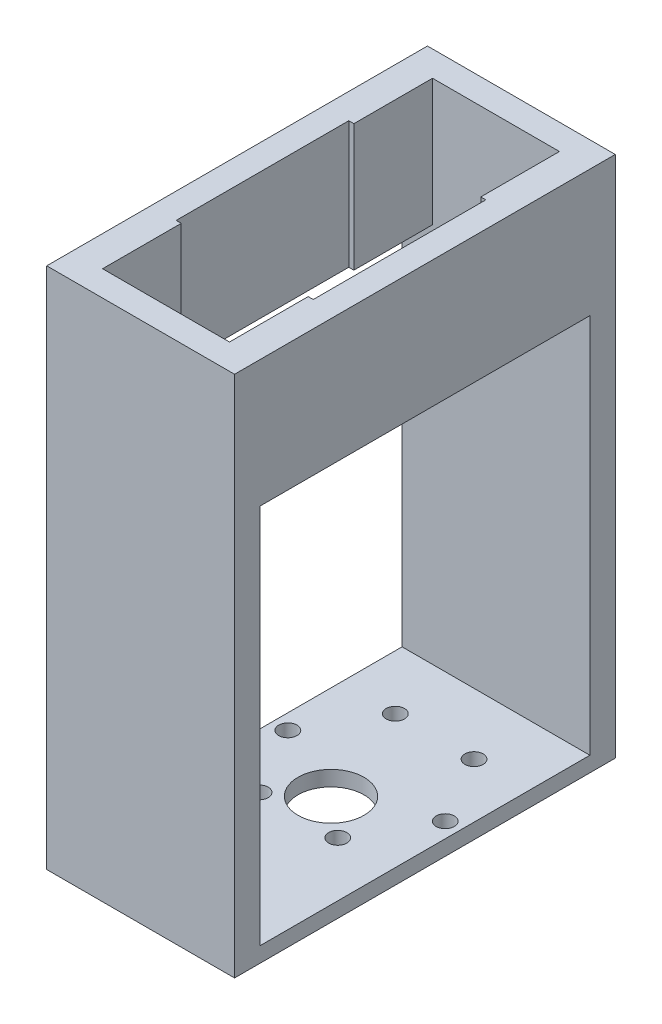
SolidWorks part; units mm, degrees
ref_plane "Front Plane" through (0, 0, 0) normal (0, 0, 1) x (1, 0, 0)
ref_plane "Top Plane" through (0, 0, 0) normal (0, 1, 0) x (1, 0, 0)
ref_plane "Right Plane" through (0, 0, 0) normal (1, 0, 0) x (0, 0, -1)
sketch "Sketch2" plane through (0, 0, 0) normal (0, 1, 0) x (1, 0, 0)
  line L1 (7.75, -13.4234) -> (15.5, 0) construction
  line L2 (15.5, 0) -> (7.75, 13.4234) construction
  line L3 (7.75, 13.4234) -> (-7.75, 13.4234) construction
  line L4 (-7.75, 13.4234) -> (-15.5, 0) construction
  line L5 (-15.5, 0) -> (-7.75, -13.4234) construction
  line L6 (-7.75, -13.4234) -> (7.75, -13.4234) construction
  circle A0 centre (0, 0) radius 13.4234 construction
  circle A1 centre (-15.5, 0) radius 1.8
  circle A2 centre (-7.75, 13.4234) radius 1.8
  circle A3 centre (7.75, 13.4234) radius 1.8
  circle A4 centre (15.5, 0) radius 1.8
  circle A5 centre (7.75, -13.4234) radius 1.8
  circle A6 centre (-7.75, -13.4234) radius 1.8
  circle A7 centre (0, 0) radius 18.5
  dimension "D2" = 3.6
  dimension "D3" = 37
  dimension "D1" = 31
extrude "Boss-Extrude1" add sketch "Sketch2" along normal blind 3
sketch "Sketch3" plane through (0, 3, 0) normal (0, 1, 0) x (1, 0, 0)
  line L0 (0, 0) -> (0, -7) construction
  circle A0 centre (0, -7) radius 6.5
  dimension "D2" = 13
  dimension "D1" = 7
extrude "Cut-Extrude1" cut sketch "Sketch3" against normal blind 3
sketch "Sketch4" plane through (0, 3, 0) normal (0, 1, 0) x (1, 0, 0)
  line L1 (-18.5, 30.5) -> (18.5, 30.5)
  line L4 (-18.5, -44.5) -> (18.5, -44.5)
  line L6 (-18.5, -44.5) -> (-18.5, 30.5)
  line L7 (18.5, 30.5) -> (18.5, -44.5)
  line L8 (0, -7) -> (2.9813, -7) construction
  circle A1 centre (0, 0) radius 18.5
  circle A2 centre (0, 0) radius 18.5
  point P7 (18.5, -7)
  circle M11 centre (0, 0) radius 18.5
  dimension "D2" = 75
  dimension "D1" = 0
extrude "Boss-Extrude2" add sketch "Sketch4" against normal up to surface (3 mm away) contours L7 L1 L6 M11 | L7 L6 L4 M11 region at (0, 3, -21.9811) region at (0, 3, 29.2305) up to face at (0, 0, 13.5)
sketch "Sketch5" plane through (0, 3, 0) normal (0, 1, 0) x (1, 0, 0)
  line L0 (18.5, 30.5) -> (18.5, -44.5) construction
  line L1 (-18.5, 30.5) -> (18.5, 30.5)
  line L2 (-18.5, 30.5) -> (-18.5, 25.5)
  line L3 (-18.5, 25.5) -> (18.5, 25.5)
  line L4 (18.5, 30.5) -> (18.5, 25.5)
  line L6 (-18.5, -44.5) -> (18.5, -44.5)
  line L7 (-18.5, -44.5) -> (-18.5, -39.5)
  line L8 (-18.5, -39.5) -> (18.5, -39.5)
  line L9 (18.5, -44.5) -> (18.5, -39.5)
  dimension "D1" = 5
extrude "Boss-Extrude3" add sketch "Sketch5" along normal blind 80
sketch "Sketch6" plane through (0, 83, 0) normal (0, 1, 0) x (1, 0, 0)
  line L0 (18.5, 25.5) -> (18.5, -39.5) construction
  line L1 (-18.5, 25.5) -> (18.5, 25.5)
  line L2 (-18.5, 25.5) -> (-18.5, 10)
  line L3 (-18.5, 10) -> (18.5, 10)
  line L4 (18.5, 25.5) -> (18.5, 10)
  line L6 (-18.5, -39.5) -> (18.5, -39.5)
  line L7 (-18.5, -39.5) -> (-18.5, -24)
  line L8 (-18.5, -24) -> (18.5, -24)
  line L9 (18.5, -39.5) -> (18.5, -24)
  dimension "D1" = 34
extrude "Boss-Extrude4" add sketch "Sketch6" against normal blind 5
sketch "Sketch7" plane through (0, 83, 0) normal (0, 1, 0) x (1, 0, 0)
  line L0 (18.5, 30.5) -> (-18.5, 30.5) construction
  line L1 (-18.5, 10) -> (-12.5, 10)
  line L2 (-18.5, 10) -> (-18.5, 30.5)
  line L3 (-18.5, 30.5) -> (-12.5, 30.5)
  line L4 (-12.5, 10) -> (-12.5, 30.5)
  line L5 (18.5, 10) -> (12.5, 10)
  line L6 (18.5, 10) -> (18.5, 30.5)
  line L7 (18.5, 30.5) -> (12.5, 30.5)
  line L8 (12.5, 10) -> (12.5, 30.5)
  line L9 (-18.5, -24) -> (-12.5, -24)
  line L10 (-18.5, -24) -> (-18.5, -44.5)
  line L11 (-18.5, -44.5) -> (-12.5, -44.5)
  line L12 (-12.5, -24) -> (-12.5, -44.5)
  line L13 (18.5, -24) -> (12.5, -24)
  line L14 (18.5, -24) -> (18.5, -44.5)
  line L15 (18.5, -44.5) -> (12.5, -44.5)
  line L16 (12.5, -24) -> (12.5, -44.5)
  dimension "D1" = 25
extrude "Boss-Extrude5" add sketch "Sketch7" along normal blind 20
sketch "Sketch8" plane through (0, 83, 0) normal (0, 1, 0) x (1, 0, 0)
  line L0 (-12.5, 10) -> (-12.5, 25.5)
  line L1 (-12.5, 10) -> (-12.5, 30.5) construction
  line L2 (-12.5, 25.5) -> (12.5, 25.5)
  line L3 (12.5, 30.5) -> (12.5, 10) construction
  line L4 (12.5, 25.5) -> (12.5, 10)
  line L5 (12.5, 10) -> (-12.5, 10)
  line L6 (-12.5, -24) -> (12.5, -24)
  line L7 (12.5, -24) -> (12.5, -39.5)
  line L8 (12.5, -24) -> (12.5, -44.5) construction
  line L9 (12.5, -39.5) -> (-12.5, -39.5)
  line L10 (-12.5, -44.5) -> (-12.5, -24) construction
  line L11 (-12.5, -39.5) -> (-12.5, -24)
  line L12 (-18.5, 25.5) -> (18.5, 25.5) construction
  line L13 (18.5, -39.5) -> (-18.5, -39.5) construction
extrude "Cut-Extrude2" cut sketch "Sketch8" against normal blind 10
sketch "Sketch9" plane through (0, 83, 0) normal (0, 1, 0) x (1, 0, 0)
  line L0 (12.5, 30.5) -> (12.5, 10) construction
  line L1 (-12.5, 30.5) -> (12.5, 30.5)
  line L2 (-12.5, 30.5) -> (-12.5, 25.5)
  line L3 (-12.5, 25.5) -> (12.5, 25.5)
  line L4 (12.5, 30.5) -> (12.5, 25.5)
  line L5 (-18.5, 25.5) -> (18.5, 25.5) construction
  line L7 (-12.5, -39.5) -> (12.5, -39.5)
  line L8 (-12.5, -39.5) -> (-12.5, -44.5)
  line L9 (-12.5, -44.5) -> (12.5, -44.5)
  line L10 (12.5, -39.5) -> (12.5, -44.5)
extrude "Boss-Extrude6" add sketch "Sketch9" along normal up to surface (20 mm away) up to face at (-15.5, 103, -20.25)
sketch "Sketch10" plane through (0, 0, 24) normal (0, 0, -1) x (-1, 0, 0)
  line L0 (12.5, 78) -> (18.5, 78) construction
  line L1 (18.5, 103) -> (13.5, 103)
  line L2 (18.5, 103) -> (18.5, 78)
  line L3 (18.5, 78) -> (13.5, 78)
  line L4 (13.5, 103) -> (13.5, 78)
  line L5 (-18.5, 78) -> (-12.5, 78) construction
  line L6 (-18.5, 103) -> (-13.5, 103)
  line L7 (-18.5, 103) -> (-18.5, 78)
  line L8 (-18.5, 78) -> (-13.5, 78)
  line L9 (-13.5, 103) -> (-13.5, 78)
  dimension "D1" = 5
extrude "Boss-Extrude7" add sketch "Sketch10" along normal up to next
